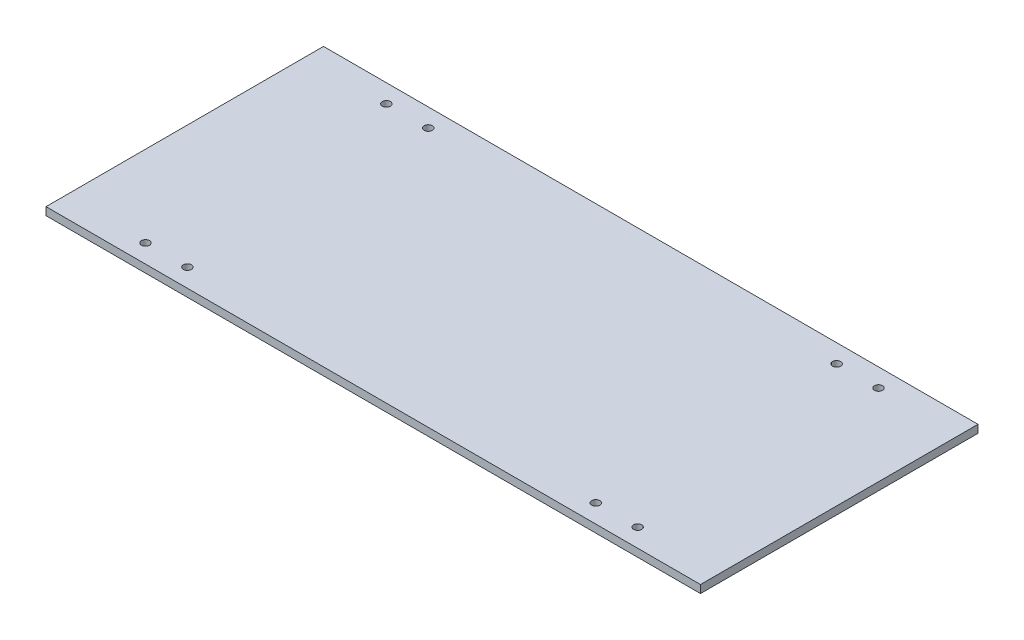
SolidWorks part; units mm, degrees
ref_plane "Front Plane" through (0, 0, 0) normal (0, 0, 1) x (1, 0, 0)
ref_plane "Top Plane" through (0, 0, 0) normal (0, 1, 0) x (1, 0, 0)
ref_plane "Right Plane" through (0, 0, 0) normal (1, 0, 0) x (0, 0, -1)
sketch "Sketch1" plane through (0, 0, 0) normal (0, 1, 0) x (1, 0, 0)
  line L0 (125, 106) -> (125, 0) construction
  line L1 (0, 106) -> (250, 106)
  line L2 (0, 106) -> (0, 0)
  line L3 (0, 0) -> (250, 0)
  line L4 (250, 106) -> (250, 0)
  line L5 (0, 53) -> (250, 53) construction
  circle A0 centre (31, 99) radius 1.55
  circle A1 centre (47, 99) radius 1.55
  circle A2 centre (203, 99) radius 1.55
  circle A3 centre (219, 99) radius 1.55
  circle A4 centre (219, 7) radius 1.55
  circle A5 centre (203, 7) radius 1.55
  circle A6 centre (47, 7) radius 1.55
  circle A7 centre (31, 7) radius 1.55
  dimension "D2" = 3.1
  dimension "D1" = 250
  dimension "D3" = 16
  dimension "D5" = 7
  dimension "D6" = 99
  dimension "D4" = 78
extrude "Boss-Extrude1" add sketch "Sketch1" along normal blind 3
equation "\"cf_tube_outer_diameter\"= 25mm"
equation "\"cf_tube_inner_diameter\" = 21mm"
equation "\"mid_plate_mid_to_top\" = 100mm"
equation "\"mid_plate_mid_to_bottom\" = 30mm"
equation "\"mid_plate_horizontal_spacing\"=250mm"
equation "\"cf_plate_thickness\" =4mm"
equation "\"mid_tube_length\" = 500mm"
equation "\"mid_support_plate_distance\" = 250mm"
equation "\"M3_hole_diameter\" = 3.1mm"
equation "\" cf_tube_outer_diameter\"= 25mm"
equation "\"D2@Sketch1\"=\"M3_hole_diameter\""
